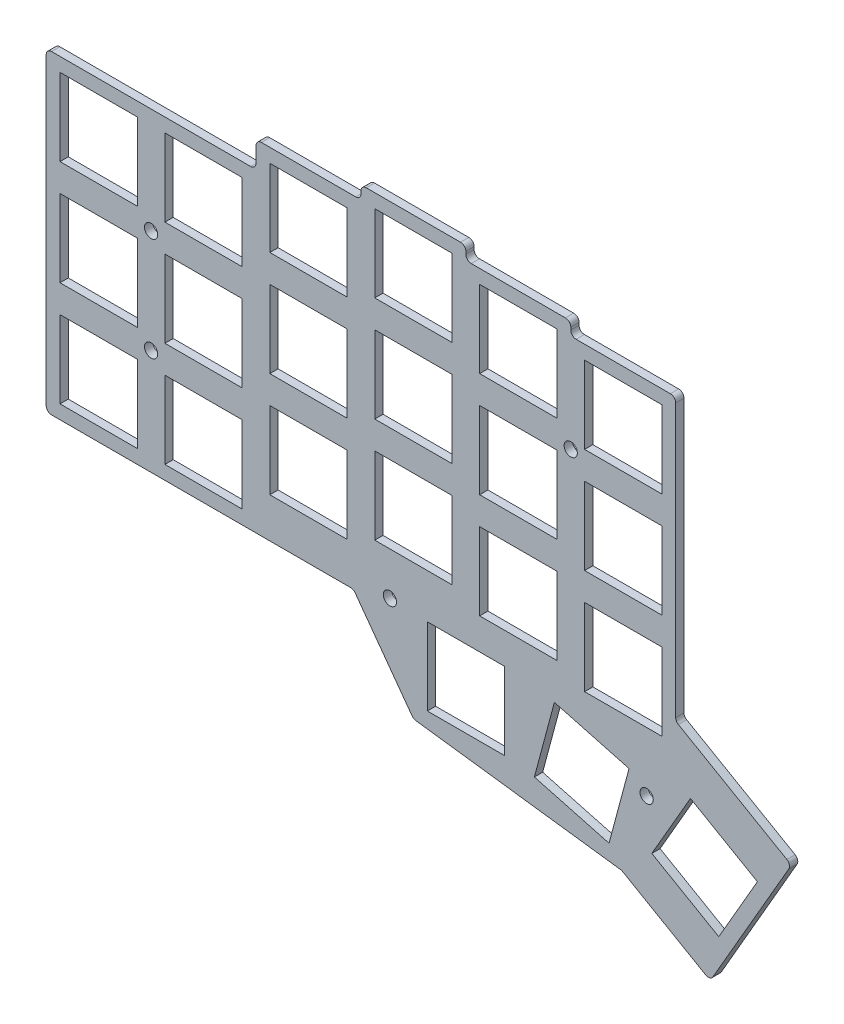
SolidWorks part; units mm, degrees
ref_plane "Front Plane" through (0, 0, 0) normal (0, 0, 1) x (1, 0, 0)
ref_plane "Top Plane" through (0, 0, 0) normal (0, 1, 0) x (1, 0, 0)
ref_plane "Right Plane" through (0, 0, 0) normal (1, 0, 0) x (0, 0, -1)
sketch "Model" plane through (0, 0, 0) normal (0, 0, 1) x (1, 0, 0)
  line L0 (-21.8431, 7.4481) -> (-8.6148, 30.3792)
  line L1 (-38.0636, 15.3297) -> (-23.771, 7.0696)
  line L2 (-75.3888, 20.2293) -> (-38.7189, 15.4592)
  line L3 (-86.2854, 34.8343) -> (-75.7419, 20.3766)
  line L4 (-29.1405, 92.9799) -> (-29.1405, 91.7303)
  line L5 (-8.8891, 91.2299) -> (-28.6402, 91.2299)
  line L6 (-8.3888, 90.7295) -> (-8.3888, 31.2555)
  line L7 (-86.6385, 34.9791) -> (-141.6396, 34.9791)
  line L8 (-142.1399, 90.7295) -> (-142.1399, 35.4795)
  line L9 (-104.6394, 91.2299) -> (-141.6396, 91.2299)
  line L10 (-104.139, 95.4793) -> (-104.139, 91.7303)
  line L11 (-85.6402, 95.9797) -> (-103.6387, 95.9797)
  line L12 (-85.1399, 97.7297) -> (-85.1399, 96.4801)
  line L13 (-67.6393, 98.2301) -> (-84.6395, 98.2301)
  line L14 (-67.1389, 96.4801) -> (-67.1389, 97.7297)
  line L15 (-48.6401, 95.9797) -> (-66.6385, 95.9797)
  line L16 (-48.1397, 93.9807) -> (-48.1397, 95.4793)
  line L17 (-29.6384, 93.4803) -> (-47.6393, 93.4803)
  line L18 (135.1563, 30.6526) -> (116.2359, 41.5721)
  line L19 (123.1828, 7.2669) -> (135.5373, 28.7222)
  line L20 (106.9623, 15.1485) -> (121.2549, 6.8884)
  line L21 (69.6371, 20.0481) -> (106.307, 15.278)
  line L22 (58.7405, 34.6531) -> (69.284, 20.1955)
  line L23 (115.8854, 92.7987) -> (115.8828, 42.2376)
  line L24 (58.3874, 34.7979) -> (3.3863, 34.7979)
  line L25 (2.886, 90.5483) -> (2.886, 35.2983)
  line L26 (40.3865, 91.0487) -> (3.3863, 91.0487)
  line L27 (40.8869, 95.2981) -> (40.8869, 91.5491)
  line L28 (59.3857, 95.7985) -> (41.3872, 95.7985)
  line L29 (59.886, 97.5485) -> (59.886, 96.2989)
  line L30 (77.3866, 98.0489) -> (60.3864, 98.0489)
  line L31 (77.887, 96.2989) -> (77.887, 97.5485)
  line L32 (96.3858, 95.7985) -> (78.3874, 95.7985)
  line L33 (96.8862, 93.7995) -> (96.8862, 95.2981)
  line L34 (115.3875, 93.2991) -> (97.3866, 93.2991)
  line L35 (20.1915, -96.2476) -> (6.9631, -73.3165)
  line L36 (36.4119, -88.366) -> (22.1193, -96.6261)
  line L37 (73.7371, -83.4663) -> (37.0672, -88.2365)
  line L38 (84.6337, -68.8614) -> (74.0902, -83.319)
  line L39 (27.4889, -10.7157) -> (27.4889, -11.9654)
  line L40 (7.2375, -12.4658) -> (26.9885, -12.4658)
  line L41 (6.7371, -12.9662) -> (6.7371, -72.4402)
  line L42 (84.9868, -68.7166) -> (139.9879, -68.7166)
  line L43 (140.4883, -12.9662) -> (140.4883, -68.2162)
  line L44 (102.9878, -12.4658) -> (139.9879, -12.4658)
  line L45 (102.4874, -8.2164) -> (102.4874, -11.9654)
  line L46 (83.9886, -7.716) -> (101.987, -7.716)
  line L47 (83.4882, -5.9659) -> (83.4882, -7.2156)
  line L48 (65.9876, -5.4656) -> (82.9878, -5.4656)
  line L49 (65.4872, -7.2156) -> (65.4872, -5.9659)
  line L50 (46.9884, -7.716) -> (64.9869, -7.716)
  line L51 (46.488, -9.715) -> (46.488, -8.2164)
  line L52 (27.9867, -10.2154) -> (45.9877, -10.2154)
  line L53 (-136.808, -73.043) -> (-117.8876, -62.1236)
  line L54 (-124.8344, -96.4288) -> (-137.189, -74.9734)
  line L55 (-108.614, -88.5472) -> (-122.9066, -96.8073)
  line L56 (-71.2888, -83.6475) -> (-107.9587, -88.4176)
  line L57 (-60.3922, -69.0425) -> (-70.9357, -83.5002)
  line L58 (-117.537, -10.8969) -> (-117.5345, -61.4581)
  line L59 (-60.0391, -68.8978) -> (-5.038, -68.8978)
  line L60 (-4.5376, -13.1474) -> (-4.5376, -68.3974)
  line L61 (-42.0381, -12.647) -> (-5.038, -12.647)
  line L62 (-42.5385, -8.3976) -> (-42.5385, -12.1466)
  line L63 (-61.0373, -7.8972) -> (-43.0389, -7.8972)
  line L64 (-61.5377, -6.1471) -> (-61.5377, -7.3968)
  line L65 (-79.0383, -5.6467) -> (-62.0381, -5.6467)
  line L66 (-79.5387, -7.3968) -> (-79.5387, -6.1471)
  line L67 (-98.0375, -7.8972) -> (-80.039, -7.8972)
  line L68 (-98.5378, -9.8962) -> (-98.5378, -8.3976)
  line L69 (-117.0392, -10.3965) -> (-99.0382, -10.3965)
  line L70 (138.9148, 92.1117) -> (138.9148, 33.3582)
  line L71 (138.1649, 32.9251) -> (119.446, 43.7282)
  line L72 (119.196, 44.1613) -> (119.196, 92.1092)
  line L73 (119.6959, 92.6092) -> (138.4148, 92.6117)
  line L74 (-140.5665, -11.584) -> (-140.5665, -70.3375)
  line L75 (-139.8166, -70.7706) -> (-121.0977, -59.9674)
  line L76 (-120.8476, -59.5344) -> (-120.8476, -11.5865)
  line L77 (-121.3476, -11.0865) -> (-140.0664, -11.084)
  line L78 (18.8966, 74.9256) -> (4.8966, 74.9256)
  line L79 (4.8966, 74.9256) -> (4.8966, 88.9256)
  line L80 (4.8966, 88.9256) -> (18.8966, 88.9256)
  line L81 (18.8966, 88.9256) -> (18.8966, 74.9256)
  line L82 (18.8966, 55.9256) -> (4.8966, 55.9256)
  line L83 (4.8966, 55.9256) -> (4.8966, 69.9256)
  line L84 (4.8966, 69.9256) -> (18.8966, 69.9256)
  line L85 (18.8966, 69.9256) -> (18.8966, 55.9256)
  line L86 (18.8966, 36.9256) -> (4.8966, 36.9256)
  line L87 (4.8966, 36.9256) -> (4.8966, 50.9256)
  line L88 (4.8966, 50.9256) -> (18.8966, 50.9256)
  line L89 (18.8966, 50.9256) -> (18.8966, 36.9256)
  line L90 (37.8948, 74.9262) -> (23.8948, 74.9262)
  line L91 (23.8948, 74.9262) -> (23.8948, 88.9262)
  line L92 (23.8948, 88.9262) -> (37.8948, 88.9262)
  line L93 (37.8948, 88.9262) -> (37.8948, 74.9262)
  line L94 (37.8948, 55.9262) -> (23.8948, 55.9262)
  line L95 (23.8948, 55.9262) -> (23.8948, 69.9262)
  line L96 (23.8948, 69.9262) -> (37.8948, 69.9262)
  line L97 (37.8948, 69.9262) -> (37.8948, 55.9262)
  line L98 (37.8948, 36.9262) -> (23.8948, 36.9262)
  line L99 (23.8948, 36.9262) -> (23.8948, 50.9262)
  line L100 (23.8948, 50.9262) -> (37.8948, 50.9262)
  line L101 (37.8948, 50.9262) -> (37.8948, 36.9262)
  line L102 (56.895, 79.671) -> (42.895, 79.671)
  line L103 (42.895, 79.671) -> (42.895, 93.671)
  line L104 (42.895, 93.671) -> (56.895, 93.671)
  line L105 (56.895, 93.671) -> (56.895, 79.671)
  line L106 (56.895, 60.6711) -> (42.895, 60.6711)
  line L107 (42.895, 60.6711) -> (42.895, 74.6711)
  line L108 (42.895, 74.6711) -> (56.895, 74.6711)
  line L109 (56.895, 74.6711) -> (56.895, 60.6711)
  line L110 (56.895, 41.6711) -> (42.895, 41.6711)
  line L111 (42.895, 41.6711) -> (42.895, 55.6711)
  line L112 (42.895, 55.6711) -> (56.895, 55.6711)
  line L113 (56.895, 55.6711) -> (56.895, 41.6711)
  line L114 (75.897, 82.0499) -> (61.897, 82.0499)
  line L115 (61.897, 82.0499) -> (61.897, 96.0499)
  line L116 (61.897, 96.0499) -> (75.897, 96.0499)
  line L117 (75.897, 96.0499) -> (75.897, 82.0499)
  line L118 (75.897, 63.0499) -> (61.897, 63.0499)
  line L119 (61.897, 63.0499) -> (61.897, 77.0499)
  line L120 (61.897, 77.0499) -> (75.897, 77.0499)
  line L121 (75.897, 77.0499) -> (75.897, 63.0499)
  line L122 (75.897, 44.0499) -> (61.897, 44.0499)
  line L123 (61.897, 44.0499) -> (61.897, 58.0499)
  line L124 (61.897, 58.0499) -> (75.897, 58.0499)
  line L125 (75.897, 58.0499) -> (75.897, 44.0499)
  line L126 (94.8982, 79.6753) -> (80.8982, 79.6753)
  line L127 (80.8982, 79.6753) -> (80.8982, 93.6753)
  line L128 (80.8982, 93.6753) -> (94.8982, 93.6753)
  line L129 (94.8982, 93.6753) -> (94.8982, 79.6753)
  line L130 (94.8982, 60.6753) -> (80.8982, 60.6753)
  line L131 (80.8982, 60.6753) -> (80.8982, 74.6753)
  line L132 (80.8982, 74.6753) -> (94.8982, 74.6753)
  line L133 (94.8982, 74.6753) -> (94.8982, 60.6753)
  line L134 (94.8982, 41.6753) -> (80.8982, 41.6753)
  line L135 (80.8982, 41.6753) -> (80.8982, 55.6753)
  line L136 (80.8982, 55.6753) -> (94.8982, 55.6753)
  line L137 (94.8982, 55.6753) -> (94.8982, 41.6753)
  line L138 (113.9, 77.2905) -> (99.9, 77.2905)
  line L139 (99.9, 77.2905) -> (99.9, 91.2905)
  line L140 (99.9, 91.2905) -> (113.9, 91.2905)
  line L141 (113.9, 91.2905) -> (113.9, 77.2905)
  line L142 (113.9, 58.2905) -> (99.9, 58.2905)
  line L143 (99.9, 58.2905) -> (99.9, 72.2905)
  line L144 (99.9, 72.2905) -> (113.9, 72.2905)
  line L145 (113.9, 72.2905) -> (113.9, 58.2905)
  line L146 (113.9, 39.2905) -> (99.9, 39.2905)
  line L147 (99.9, 39.2905) -> (99.9, 53.2905)
  line L148 (99.9, 53.2905) -> (113.9, 53.2905)
  line L149 (113.9, 53.2905) -> (113.9, 39.2905)
  line L150 (85.4166, 22.0174) -> (71.4166, 22.0174)
  line L151 (71.4166, 22.0174) -> (71.4166, 36.0174)
  line L152 (71.4166, 36.0174) -> (85.4166, 36.0174)
  line L153 (85.4166, 36.0174) -> (85.4166, 22.0174)
  line L154 (104.3289, 17.734) -> (90.806, 21.3575)
  line L155 (90.806, 21.3575) -> (94.4294, 34.8805)
  line L156 (94.4294, 34.8805) -> (107.9524, 31.257)
  line L157 (107.9524, 31.257) -> (104.3289, 17.734)
  line L158 (124.1994, 13.0049) -> (112.075, 20.0049)
  line L159 (112.075, 20.0049) -> (119.075, 32.1293)
  line L160 (119.075, 32.1293) -> (131.1994, 25.1293)
  line L161 (131.1994, 25.1293) -> (124.1994, 13.0049)
  line L162 (-20.5483, -28.7701) -> (-6.5483, -28.7701)
  line L163 (-6.5483, -28.7701) -> (-6.5483, -14.7701)
  line L164 (-6.5483, -14.7701) -> (-20.5483, -14.7701)
  line L165 (-20.5483, -14.7701) -> (-20.5483, -28.7701)
  line L166 (-20.5483, -47.7701) -> (-6.5483, -47.7701)
  line L167 (-6.5483, -47.7701) -> (-6.5483, -33.7701)
  line L168 (-6.5483, -33.7701) -> (-20.5483, -33.7701)
  line L169 (-20.5483, -33.7701) -> (-20.5483, -47.7701)
  line L170 (-20.5483, -66.7701) -> (-6.5483, -66.7701)
  line L171 (-6.5483, -66.7701) -> (-6.5483, -52.7701)
  line L172 (-6.5483, -52.7701) -> (-20.5483, -52.7701)
  line L173 (-20.5483, -52.7701) -> (-20.5483, -66.7701)
  line L174 (-39.5464, -28.7694) -> (-25.5464, -28.7694)
  line L175 (-25.5464, -28.7694) -> (-25.5464, -14.7694)
  line L176 (-25.5464, -14.7694) -> (-39.5464, -14.7694)
  line L177 (-39.5464, -14.7694) -> (-39.5464, -28.7694)
  line L178 (-39.5464, -47.7694) -> (-25.5464, -47.7694)
  line L179 (-25.5464, -47.7694) -> (-25.5464, -33.7694)
  line L180 (-25.5464, -33.7694) -> (-39.5464, -33.7694)
  line L181 (-39.5464, -33.7694) -> (-39.5464, -47.7694)
  line L182 (-39.5464, -66.7694) -> (-25.5464, -66.7694)
  line L183 (-25.5464, -66.7694) -> (-25.5464, -52.7694)
  line L184 (-25.5464, -52.7694) -> (-39.5464, -52.7694)
  line L185 (-39.5464, -52.7694) -> (-39.5464, -66.7694)
  line L186 (-58.5467, -24.0246) -> (-44.5467, -24.0246)
  line L187 (-44.5467, -24.0246) -> (-44.5467, -10.0246)
  line L188 (-44.5467, -10.0246) -> (-58.5467, -10.0246)
  line L189 (-58.5467, -10.0246) -> (-58.5467, -24.0246)
  line L190 (-58.5467, -43.0246) -> (-44.5467, -43.0246)
  line L191 (-44.5467, -43.0246) -> (-44.5467, -29.0246)
  line L192 (-44.5467, -29.0246) -> (-58.5467, -29.0246)
  line L193 (-58.5467, -29.0246) -> (-58.5467, -43.0246)
  line L194 (-58.5467, -62.0246) -> (-44.5467, -62.0246)
  line L195 (-44.5467, -62.0246) -> (-44.5467, -48.0246)
  line L196 (-44.5467, -48.0246) -> (-58.5467, -48.0246)
  line L197 (-58.5467, -48.0246) -> (-58.5467, -62.0246)
  line L198 (-77.5486, -21.6458) -> (-63.5486, -21.6458)
  line L199 (-63.5486, -21.6458) -> (-63.5486, -7.6458)
  line L200 (-63.5486, -7.6458) -> (-77.5486, -7.6458)
  line L201 (-77.5486, -7.6458) -> (-77.5486, -21.6458)
  line L202 (-77.5486, -40.6458) -> (-63.5486, -40.6458)
  line L203 (-63.5486, -40.6458) -> (-63.5486, -26.6458)
  line L204 (-63.5486, -26.6458) -> (-77.5486, -26.6458)
  line L205 (-77.5486, -26.6458) -> (-77.5486, -40.6458)
  line L206 (-77.5486, -59.6458) -> (-63.5486, -59.6458)
  line L207 (-63.5486, -59.6458) -> (-63.5486, -45.6458)
  line L208 (-63.5486, -45.6458) -> (-77.5486, -45.6458)
  line L209 (-77.5486, -45.6458) -> (-77.5486, -59.6458)
  line L210 (-96.5499, -24.0204) -> (-82.5499, -24.0204)
  line L211 (-82.5499, -24.0204) -> (-82.5499, -10.0204)
  line L212 (-82.5499, -10.0204) -> (-96.5499, -10.0204)
  line L213 (-96.5499, -10.0204) -> (-96.5499, -24.0204)
  line L214 (-96.5499, -43.0203) -> (-82.5499, -43.0203)
  line L215 (-82.5499, -43.0203) -> (-82.5499, -29.0203)
  line L216 (-82.5499, -29.0203) -> (-96.5499, -29.0203)
  line L217 (-96.5499, -29.0203) -> (-96.5499, -43.0203)
  line L218 (-96.5499, -62.0203) -> (-82.5499, -62.0203)
  line L219 (-82.5499, -62.0203) -> (-82.5499, -48.0203)
  line L220 (-82.5499, -48.0203) -> (-96.5499, -48.0203)
  line L221 (-96.5499, -48.0203) -> (-96.5499, -62.0203)
  line L222 (-115.5516, -26.4052) -> (-101.5516, -26.4052)
  line L223 (-101.5516, -26.4052) -> (-101.5516, -12.4052)
  line L224 (-101.5516, -12.4052) -> (-115.5516, -12.4052)
  line L225 (-115.5516, -12.4052) -> (-115.5516, -26.4052)
  line L226 (-115.5516, -45.4052) -> (-101.5516, -45.4052)
  line L227 (-101.5516, -45.4052) -> (-101.5516, -31.4052)
  line L228 (-101.5516, -31.4052) -> (-115.5516, -31.4052)
  line L229 (-115.5516, -31.4052) -> (-115.5516, -45.4052)
  line L230 (-115.5516, -64.4052) -> (-101.5516, -64.4052)
  line L231 (-101.5516, -64.4052) -> (-101.5516, -50.4052)
  line L232 (-101.5516, -50.4052) -> (-115.5516, -50.4052)
  line L233 (-115.5516, -50.4052) -> (-115.5516, -64.4052)
  line L234 (-87.0683, -81.6783) -> (-73.0683, -81.6783)
  line L235 (-73.0683, -81.6783) -> (-73.0683, -67.6783)
  line L236 (-73.0683, -67.6783) -> (-87.0683, -67.6783)
  line L237 (-87.0683, -67.6783) -> (-87.0683, -81.6783)
  line L238 (-105.9806, -85.9616) -> (-92.4576, -82.3382)
  line L239 (-92.4576, -82.3382) -> (-96.0811, -68.8152)
  line L240 (-96.0811, -68.8152) -> (-109.6041, -72.4387)
  line L241 (-109.6041, -72.4387) -> (-105.9806, -85.9616)
  line L242 (-125.851, -90.6908) -> (-113.7267, -83.6908)
  line L243 (-113.7267, -83.6908) -> (-120.7267, -71.5664)
  line L244 (-120.7267, -71.5664) -> (-132.851, -78.5664)
  line L245 (-132.851, -78.5664) -> (-125.851, -90.6908)
  spline S0 degree 3 poles (-8.6153, 30.3807) (-8.4626, 30.6458) (-8.3842, 30.9472) (-8.3882, 31.2532) knots 0 0 0 0 1 1 1 1
  spline S1 degree 3 poles (-21.8439, 7.4422) (-21.8429, 7.4437) (-21.8419, 7.4453) (-21.8408, 7.4468) knots 1 1 1 1 2 2 2 2
  spline S2 degree 3 poles (-23.769, 7.0673) (-23.1339, 6.6392) (-22.272, 6.8071) (-21.8439, 7.4422) knots 0 0 0 0 1 1 1 1
  spline S3 degree 3 poles (-38.063, 15.3284) (-38.2765, 15.3928) (-38.4957, 15.4362) (-38.7176, 15.4579) knots 0 0 0 0 1 1 1 1
  spline S4 degree 3 poles (-75.7416, 20.3746) (-75.6478, 20.2809) (-75.5206, 20.2283) (-75.3881, 20.2283) knots 0 0 0 0 1 1 1 1
  spline S5 degree 3 poles (-29.1383, 92.9782) (-29.1382, 93.2543) (-29.362, 93.4782) (-29.6381, 93.4783) knots 0 0 0 0 1 1 1 1
  spline S6 degree 3 poles (-29.1383, 91.7282) (-29.1383, 91.4521) (-28.9145, 91.2282) (-28.6384, 91.2281) (-28.6383, 91.2281) (-28.6382, 91.2281) (-28.6381, 91.2281) knots 0 0 0 0 1 1 1 2 2 2 2
  spline S7 degree 3 poles (-86.2846, 34.8318) (-86.3784, 34.9256) (-86.5056, 34.9783) (-86.6385, 34.9791) knots 0 0 0 0 1 1 1 1
  spline S8 degree 3 poles (-142.1382, 35.4782) (-142.1381, 35.2021) (-141.9142, 34.9783) (-141.6381, 34.9783) knots 0 0 0 0 1 1 1 1
  spline S9 degree 3 poles (-141.638, 91.2281) (-141.9142, 91.2282) (-142.1381, 91.0044) (-142.1382, 90.7282) knots 0 0 0 0 1 1 1 1
  spline S10 degree 3 poles (-104.6382, 91.2281) (-104.362, 91.228) (-104.1381, 91.4518) (-104.138, 91.728) (-104.138, 91.7281) (-104.138, 91.7281) (-104.138, 91.7282) knots 0 0 0 0 1 1 1 2 2 2 2
  spline S11 degree 3 poles (-103.6382, 95.9781) (-103.9142, 95.9781) (-104.138, 95.7543) (-104.138, 95.4783) knots 0 0 0 0 1 1 1 1
  spline S12 degree 3 poles (-85.6382, 95.9781) (-85.3621, 95.9781) (-85.1382, 96.2019) (-85.1381, 96.478) (-85.1381, 96.4781) (-85.1381, 96.4782) (-85.1381, 96.4783) knots 0 0 0 0 1 1 1 2 2 2 2
  spline S13 degree 3 poles (-84.6382, 98.2283) (-84.9144, 98.2283) (-85.1382, 98.0044) (-85.1381, 97.7282) knots 0 0 0 0 1 1 1 1
  spline S14 degree 3 poles (-67.1381, 97.7282) (-67.1381, 98.0043) (-67.3619, 98.2283) (-67.638, 98.2283) knots 0 0 0 0 2 2 2 2
  spline S15 degree 3 poles (-67.1381, 96.4783) (-67.1382, 96.2021) (-66.9144, 95.9782) (-66.6383, 95.9781) (-66.6382, 95.9781) (-66.6381, 95.9781) (-66.638, 95.9781) knots 0 0 0 0 1 1 1 2 2 2 2
  spline S16 degree 3 poles (-48.1382, 95.4783) (-48.1383, 95.7543) (-48.362, 95.9781) (-48.6381, 95.9781) knots 0 0 0 0 1 1 1 1
  spline S17 degree 3 poles (-48.1382, 93.9782) (-48.1381, 93.702) (-47.9142, 93.4782) (-47.6381, 93.4783) knots 0 0 0 0 1 1 1 1
  spline S18 degree 3 poles (-8.3882, 90.7282) (-8.3883, 91.0043) (-8.6121, 91.228) (-8.8881, 91.2281) knots 0 0 0 0 1 1 1 1
  spline S19 degree 3 poles (115.8851, 42.2368) (115.8929, 41.9725) (116.0232, 41.7268) (116.2377, 41.5721) knots 0 0 0 0 1 1 1 1
  spline S20 degree 3 poles (135.163, 30.647) (135.1614, 30.648) (135.1599, 30.6491) (135.1583, 30.6501) knots 1 1 1 1 2 2 2 2
  spline S21 degree 3 poles (135.5373, 28.7222) (135.9659, 29.3571) (135.7981, 30.2189) (135.163, 30.647) knots 0 0 0 0 1 1 1 1
  spline S22 degree 3 poles (123.182, 7.261) (123.183, 7.2625) (123.184, 7.2641) (123.1851, 7.2656) knots 1 1 1 1 2 2 2 2
  spline S23 degree 3 poles (121.2569, 6.8861) (121.892, 6.4581) (122.7539, 6.6259) (123.182, 7.261) knots 0 0 0 0 1 1 1 1
  spline S24 degree 3 poles (106.9629, 15.1472) (106.7494, 15.2117) (106.5302, 15.255) (106.3083, 15.2768) knots 0 0 0 0 1 1 1 1
  spline S25 degree 3 poles (69.2843, 20.1934) (69.3781, 20.0997) (69.5053, 20.0471) (69.6378, 20.0471) knots 0 0 0 0 1 1 1 1
  spline S26 degree 3 poles (115.8876, 92.797) (115.8877, 93.0731) (115.6639, 93.297) (115.3878, 93.2971) knots 0 0 0 0 1 1 1 1
  spline S27 degree 3 poles (58.7413, 34.6506) (58.6475, 34.7444) (58.5203, 34.7971) (58.3874, 34.7979) knots 0 0 0 0 1 1 1 1
  spline S28 degree 3 poles (2.8877, 35.297) (2.8878, 35.0209) (3.1117, 34.7971) (3.3878, 34.7971) knots 0 0 0 0 1 1 1 1
  spline S29 degree 3 poles (3.3879, 91.0469) (3.1117, 91.047) (2.8878, 90.8232) (2.8877, 90.547) knots 0 0 0 0 1 1 1 1
  spline S30 degree 3 poles (40.3877, 91.0469) (40.6639, 91.0468) (40.8878, 91.2706) (40.8879, 91.5468) (40.8879, 91.5469) (40.8879, 91.5469) (40.8879, 91.547) knots 0 0 0 0 1 1 1 2 2 2 2
  spline S31 degree 3 poles (41.3877, 95.797) (41.1117, 95.7969) (40.8879, 95.5731) (40.8879, 95.2971) knots 0 0 0 0 1 1 1 1
  spline S32 degree 3 poles (59.3877, 95.797) (59.6638, 95.7969) (59.8877, 96.0207) (59.8878, 96.2968) (59.8878, 96.2969) (59.8878, 96.297) (59.8878, 96.2971) knots 0 0 0 0 1 1 1 2 2 2 2
  spline S33 degree 3 poles (60.3877, 98.0471) (60.1115, 98.0471) (59.8877, 97.8232) (59.8878, 97.547) knots 0 0 0 0 1 1 1 1
  spline S34 degree 3 poles (77.8878, 97.547) (77.8878, 97.8232) (77.664, 98.0471) (77.3879, 98.0471) knots 0 0 0 0 2 2 2 2
  spline S35 degree 3 poles (77.8878, 96.2971) (77.8877, 96.0209) (78.1115, 95.797) (78.3876, 95.797) (78.3877, 95.797) (78.3878, 95.797) (78.3879, 95.797) knots 0 0 0 0 1 1 1 2 2 2 2
  spline S36 degree 3 poles (96.8877, 95.2971) (96.8876, 95.5731) (96.6639, 95.7969) (96.3878, 95.797) knots 0 0 0 0 1 1 1 1
  spline S37 degree 3 poles (96.8877, 93.797) (96.8878, 93.5208) (97.1117, 93.297) (97.3878, 93.2971) knots 0 0 0 0 1 1 1 1
  spline S38 degree 3 poles (6.9637, -73.315) (6.8109, -73.0499) (6.7325, -72.7484) (6.7366, -72.4425) knots 0 0 0 0 1 1 1 1
  spline S39 degree 3 poles (20.1923, -96.2535) (20.1912, -96.252) (20.1902, -96.2504) (20.1892, -96.2489) knots 1 1 1 1 2 2 2 2
  spline S40 degree 3 poles (22.1173, -96.6284) (21.4822, -97.0564) (20.6203, -96.8886) (20.1923, -96.2535) knots 0 0 0 0 1 1 1 1
  spline S41 degree 3 poles (36.4114, -88.3673) (36.6248, -88.3028) (36.844, -88.2594) (37.0659, -88.2377) knots 0 0 0 0 1 1 1 1
  spline S42 degree 3 poles (74.0899, -83.3211) (73.9962, -83.4148) (73.869, -83.4674) (73.7364, -83.4674) knots 0 0 0 0 1 1 1 1
  spline S43 degree 3 poles (27.4866, -10.7175) (27.4865, -10.4414) (27.7103, -10.2175) (27.9865, -10.2174) knots 0 0 0 0 1 1 1 1
  spline S44 degree 3 poles (27.4866, -11.9674) (27.4866, -12.2436) (27.2628, -12.4675) (26.9867, -12.4676) (26.9866, -12.4676) (26.9865, -12.4676) (26.9865, -12.4676) knots 0 0 0 0 1 1 1 2 2 2 2
  spline S45 degree 3 poles (84.633, -68.8639) (84.7267, -68.7701) (84.8539, -68.7174) (84.9868, -68.7166) knots 0 0 0 0 1 1 1 1
  spline S46 degree 3 poles (140.4865, -68.2175) (140.4864, -68.4936) (140.2625, -68.7174) (139.9864, -68.7173) knots 0 0 0 0 1 1 1 1
  spline S47 degree 3 poles (139.9864, -12.4676) (140.2625, -12.4675) (140.4864, -12.6913) (140.4865, -12.9674) knots 0 0 0 0 1 1 1 1
  spline S48 degree 3 poles (102.9865, -12.4676) (102.7103, -12.4676) (102.4864, -12.2438) (102.4864, -11.9677) (102.4864, -11.9676) (102.4864, -11.9675) (102.4864, -11.9674) knots 0 0 0 0 1 1 1 2 2 2 2
  spline S49 degree 3 poles (101.9865, -7.7175) (102.2625, -7.7176) (102.4863, -7.9413) (102.4864, -8.2174) knots 0 0 0 0 1 1 1 1
  spline S50 degree 3 poles (83.9865, -7.7175) (83.7104, -7.7176) (83.4865, -7.4938) (83.4864, -7.2176) (83.4864, -7.2176) (83.4864, -7.2175) (83.4864, -7.2174) knots 0 0 0 0 1 1 1 2 2 2 2
  spline S51 degree 3 poles (82.9865, -5.4673) (83.2627, -5.4674) (83.4865, -5.6913) (83.4864, -5.9675) knots 0 0 0 0 1 1 1 1
  spline S52 degree 3 poles (65.4865, -5.9675) (65.4864, -5.6913) (65.7102, -5.4674) (65.9863, -5.4673) knots 0 0 0 0 2 2 2 2
  spline S53 degree 3 poles (65.4865, -7.2174) (65.4865, -7.4935) (65.2627, -7.7174) (64.9866, -7.7175) (64.9865, -7.7175) (64.9864, -7.7175) (64.9863, -7.7175) knots 0 0 0 0 1 1 1 2 2 2 2
  spline S54 degree 3 poles (46.4865, -8.2174) (46.4866, -7.9413) (46.7103, -7.7176) (46.9864, -7.7175) knots 0 0 0 0 1 1 1 1
  spline S55 degree 3 poles (46.4865, -9.7175) (46.4865, -9.9937) (46.2625, -10.2175) (45.9864, -10.2174) knots 0 0 0 0 1 1 1 1
  spline S56 degree 3 poles (6.7366, -12.9674) (6.7366, -12.6914) (6.9604, -12.4676) (7.2365, -12.4676) knots 0 0 0 0 1 1 1 1
  spline S57 degree 3 poles (-117.5368, -61.4589) (-117.5446, -61.7232) (-117.6748, -61.9689) (-117.8893, -62.1236) knots 0 0 0 0 1 1 1 1
  spline S58 degree 3 poles (-136.8146, -73.0487) (-136.8131, -73.0476) (-136.8116, -73.0466) (-136.81, -73.0456) knots 1 1 1 1 2 2 2 2
  spline S59 degree 3 poles (-137.189, -74.9734) (-137.6176, -74.3386) (-137.4497, -73.4767) (-136.8146, -73.0487) knots 0 0 0 0 1 1 1 1
  spline S60 degree 3 poles (-124.8336, -96.4347) (-124.8347, -96.4331) (-124.8357, -96.4316) (-124.8367, -96.4301) knots 1 1 1 1 2 2 2 2
  spline S61 degree 3 poles (-122.9086, -96.8095) (-123.5437, -97.2376) (-124.4056, -97.0698) (-124.8336, -96.4347) knots 0 0 0 0 1 1 1 1
  spline S62 degree 3 poles (-108.6145, -88.5485) (-108.4011, -88.484) (-108.1819, -88.4406) (-107.96, -88.4189) knots 0 0 0 0 1 1 1 1
  spline S63 degree 3 poles (-70.936, -83.5022) (-71.0297, -83.596) (-71.1569, -83.6486) (-71.2895, -83.6485) knots 0 0 0 0 1 1 1 1
  spline S64 degree 3 poles (-117.5393, -10.8987) (-117.5394, -10.6226) (-117.3156, -10.3987) (-117.0394, -10.3986) knots 0 0 0 0 1 1 1 1
  spline S65 degree 3 poles (-60.3929, -69.0451) (-60.2992, -68.9513) (-60.172, -68.8986) (-60.0391, -68.8978) knots 0 0 0 0 1 1 1 1
  spline S66 degree 3 poles (-4.5394, -68.3987) (-4.5395, -68.6748) (-4.7634, -68.8986) (-5.0395, -68.8985) knots 0 0 0 0 1 1 1 1
  spline S67 degree 3 poles (-5.0395, -12.6488) (-4.7634, -12.6487) (-4.5395, -12.8725) (-4.5394, -13.1486) knots 0 0 0 0 1 1 1 1
  spline S68 degree 3 poles (-42.0394, -12.6488) (-42.3156, -12.6488) (-42.5395, -12.425) (-42.5395, -12.1489) (-42.5395, -12.1488) (-42.5395, -12.1487) (-42.5395, -12.1486) knots 0 0 0 0 1 1 1 2 2 2 2
  spline S69 degree 3 poles (-43.0394, -7.8987) (-42.7634, -7.8988) (-42.5396, -8.1225) (-42.5395, -8.3986) knots 0 0 0 0 1 1 1 1
  spline S70 degree 3 poles (-61.0394, -7.8987) (-61.3155, -7.8988) (-61.5394, -7.675) (-61.5395, -7.3988) (-61.5395, -7.3988) (-61.5395, -7.3987) (-61.5395, -7.3986) knots 0 0 0 0 1 1 1 2 2 2 2
  spline S71 degree 3 poles (-62.0394, -5.6485) (-61.7632, -5.6486) (-61.5394, -5.8725) (-61.5395, -6.1486) knots 0 0 0 0 1 1 1 1
  spline S72 degree 3 poles (-79.5394, -6.1486) (-79.5395, -5.8725) (-79.3157, -5.6486) (-79.0396, -5.6485) knots 0 0 0 0 2 2 2 2
  spline S73 degree 3 poles (-79.5394, -7.3986) (-79.5394, -7.6747) (-79.7632, -7.8986) (-80.0393, -7.8987) (-80.0394, -7.8987) (-80.0395, -7.8987) (-80.0396, -7.8987) knots 0 0 0 0 1 1 1 2 2 2 2
  spline S74 degree 3 poles (-98.5394, -8.3986) (-98.5393, -8.1225) (-98.3156, -7.8988) (-98.0395, -7.8987) knots 0 0 0 0 1 1 1 1
  spline S75 degree 3 poles (-98.5394, -9.8987) (-98.5394, -10.1748) (-98.7634, -10.3986) (-99.0395, -10.3986) knots 0 0 0 0 1 1 1 1
  spline S76 degree 3 poles (-123.6381, 52.6314) (-124.2456, 52.6314) (-124.7381, 53.1239) (-124.7381, 53.7314) (-124.7381, 54.3389) (-124.2456, 54.8314) (-123.6381, 54.8314) knots 2 2 2 2 3 3 3 4 4 4 4
  spline S77 degree 3 poles (-123.6381, 54.8314) (-123.0306, 54.8314) (-122.5381, 54.3389) (-122.5381, 53.7314) (-122.5381, 53.1239) (-123.0306, 52.6314) (-123.6381, 52.6314) knots 0 0 0 0 1 1 1 2 2 2 2
  spline S78 degree 3 poles (-123.6381, 71.3814) (-124.2456, 71.3814) (-124.7381, 71.8739) (-124.7381, 72.4814) (-124.7381, 73.0889) (-124.2456, 73.5814) (-123.6381, 73.5814) knots 2 2 2 2 3 3 3 4 4 4 4
  spline S79 degree 3 poles (-123.6381, 73.5814) (-123.0306, 73.5814) (-122.5381, 73.0889) (-122.5381, 72.4814) (-122.5381, 71.8739) (-123.0306, 71.3814) (-123.6381, 71.3814) knots 0 0 0 0 1 1 1 2 2 2 2
  spline S80 degree 3 poles (-47.6381, 75.1312) (-48.2456, 75.1312) (-48.7381, 75.6237) (-48.7381, 76.2312) (-48.7381, 76.8387) (-48.2456, 77.3312) (-47.6381, 77.3312) knots 2 2 2 2 3 3 3 4 4 4 4
  spline S81 degree 3 poles (-47.6381, 77.3312) (-47.0306, 77.3312) (-46.5381, 76.8387) (-46.5381, 76.2312) (-46.5381, 75.6237) (-47.0306, 75.1312) (-47.6381, 75.1312) knots 0 0 0 0 1 1 1 2 2 2 2
  spline S82 degree 3 poles (-80.388, 35.3813) (-80.9956, 35.3813) (-81.488, 35.8738) (-81.488, 36.4813) (-81.488, 37.0888) (-80.9956, 37.5813) (-80.388, 37.5813) knots 2 2 2 2 3 3 3 4 4 4 4
  spline S83 degree 3 poles (-80.388, 37.5813) (-79.7805, 37.5813) (-79.288, 37.0888) (-79.288, 36.4813) (-79.288, 35.8738) (-79.7805, 35.3813) (-80.388, 35.3813) knots 0 0 0 0 1 1 1 2 2 2 2
  spline S84 degree 3 poles (-33.8881, 27.6312) (-34.4956, 27.6312) (-34.9881, 28.1237) (-34.9881, 28.7312) (-34.9881, 29.3388) (-34.4956, 29.8312) (-33.8881, 29.8312) knots 2 2 2 2 3 3 3 4 4 4 4
  spline S85 degree 3 poles (-33.8881, 29.8312) (-33.2805, 29.8312) (-32.7881, 29.3388) (-32.7881, 28.7312) (-32.7881, 28.1237) (-33.2805, 27.6312) (-33.8881, 27.6312) knots 0 0 0 0 1 1 1 2 2 2 2
  spline S86 degree 3 poles (21.3878, 52.4502) (20.7803, 52.4502) (20.2878, 52.9427) (20.2878, 53.5502) (20.2878, 54.1578) (20.7803, 54.6502) (21.3878, 54.6502) knots 2 2 2 2 3 3 3 4 4 4 4
  spline S87 degree 3 poles (21.3878, 54.6502) (21.9953, 54.6502) (22.4878, 54.1578) (22.4878, 53.5502) (22.4878, 52.9427) (21.9953, 52.4502) (21.3878, 52.4502) knots 0 0 0 0 1 1 1 2 2 2 2
  spline S88 degree 3 poles (97.3878, 74.95) (96.7803, 74.95) (96.2878, 75.4425) (96.2878, 76.05) (96.2878, 76.6575) (96.7803, 77.15) (97.3878, 77.15) knots 2 2 2 2 3 3 3 4 4 4 4
  spline S89 degree 3 poles (97.3878, 77.15) (97.9953, 77.15) (98.4878, 76.6575) (98.4878, 76.05) (98.4878, 75.4425) (97.9953, 74.95) (97.3878, 74.95) knots 0 0 0 0 1 1 1 2 2 2 2
  spline S90 degree 3 poles (64.6379, 35.2001) (64.0303, 35.2001) (63.5379, 35.6926) (63.5379, 36.3001) (63.5379, 36.9076) (64.0303, 37.4001) (64.6379, 37.4001) knots 2 2 2 2 3 3 3 4 4 4 4
  spline S91 degree 3 poles (64.6379, 37.4001) (65.2454, 37.4001) (65.7379, 36.9076) (65.7379, 36.3001) (65.7379, 35.6926) (65.2454, 35.2001) (64.6379, 35.2001) knots 0 0 0 0 1 1 1 2 2 2 2
  spline S92 degree 3 poles (111.1378, 27.4501) (110.5303, 27.4501) (110.0378, 27.9425) (110.0378, 28.5501) (110.0378, 29.1576) (110.5303, 29.65) (111.1378, 29.65) knots 2 2 2 2 3 3 3 4 4 4 4
  spline S93 degree 3 poles (111.1378, 29.65) (111.7454, 29.65) (112.2378, 29.1576) (112.2378, 28.5501) (112.2378, 27.9425) (111.7454, 27.4501) (111.1378, 27.4501) knots 0 0 0 0 1 1 1 2 2 2 2
  spline S94 degree 3 poles (121.9864, -51.0642) (122.5939, -51.0642) (123.0864, -50.5718) (123.0864, -49.9642) (123.0864, -49.3567) (122.5939, -48.8642) (121.9864, -48.8642) knots 2 2 2 2 3 3 3 4 4 4 4
  spline S95 degree 3 poles (121.9864, -48.8642) (121.3789, -48.8642) (120.8864, -49.3567) (120.8864, -49.9642) (120.8864, -50.5718) (121.3789, -51.0642) (121.9864, -51.0642) knots 0 0 0 0 1 1 1 2 2 2 2
  spline S96 degree 3 poles (121.9864, -32.3142) (122.5939, -32.3142) (123.0864, -31.8218) (123.0864, -31.2142) (123.0864, -30.6067) (122.5939, -30.1142) (121.9864, -30.1142) knots 2 2 2 2 3 3 3 4 4 4 4
  spline S97 degree 3 poles (121.9864, -30.1142) (121.3789, -30.1142) (120.8864, -30.6067) (120.8864, -31.2142) (120.8864, -31.8218) (121.3789, -32.3142) (121.9864, -32.3142) knots 0 0 0 0 1 1 1 2 2 2 2
  spline S98 degree 3 poles (45.9864, -28.5644) (46.5939, -28.5644) (47.0864, -28.072) (47.0864, -27.4644) (47.0864, -26.8569) (46.5939, -26.3644) (45.9864, -26.3644) knots 2 2 2 2 3 3 3 4 4 4 4
  spline S99 degree 3 poles (45.9864, -26.3644) (45.3789, -26.3644) (44.8864, -26.8569) (44.8864, -27.4644) (44.8864, -28.072) (45.3789, -28.5644) (45.9864, -28.5644) knots 0 0 0 0 1 1 1 2 2 2 2
  spline S100 degree 3 poles (78.7364, -68.3144) (79.3439, -68.3144) (79.8364, -67.8219) (79.8364, -67.2144) (79.8364, -66.6069) (79.3439, -66.1144) (78.7364, -66.1144) knots 2 2 2 2 3 3 3 4 4 4 4
  spline S101 degree 3 poles (78.7364, -66.1144) (78.1288, -66.1144) (77.6364, -66.6069) (77.6364, -67.2144) (77.6364, -67.8219) (78.1288, -68.3144) (78.7364, -68.3144) knots 0 0 0 0 1 1 1 2 2 2 2
  spline S102 degree 3 poles (32.2364, -76.0644) (32.8439, -76.0644) (33.3364, -75.5719) (33.3364, -74.9644) (33.3364, -74.3569) (32.8439, -73.8644) (32.2364, -73.8644) knots 2 2 2 2 3 3 3 4 4 4 4
  spline S103 degree 3 poles (32.2364, -73.8644) (31.6289, -73.8644) (31.1364, -74.3569) (31.1364, -74.9644) (31.1364, -75.5719) (31.6289, -76.0644) (32.2364, -76.0644) knots 0 0 0 0 1 1 1 2 2 2 2
  spline S104 degree 3 poles (-23.0395, -51.2454) (-22.432, -51.2454) (-21.9395, -50.7529) (-21.9395, -50.1454) (-21.9395, -49.5379) (-22.432, -49.0454) (-23.0395, -49.0454) knots 2 2 2 2 3 3 3 4 4 4 4
  spline S105 degree 3 poles (-23.0395, -49.0454) (-23.647, -49.0454) (-24.1395, -49.5379) (-24.1395, -50.1454) (-24.1395, -50.7529) (-23.647, -51.2454) (-23.0395, -51.2454) knots 0 0 0 0 1 1 1 2 2 2 2
  spline S106 degree 3 poles (-99.0395, -28.7456) (-98.432, -28.7456) (-97.9395, -28.2531) (-97.9395, -27.6456) (-97.9395, -27.0381) (-98.432, -26.5456) (-99.0395, -26.5456) knots 2 2 2 2 3 3 3 4 4 4 4
  spline S107 degree 3 poles (-99.0395, -26.5456) (-99.647, -26.5456) (-100.1395, -27.0381) (-100.1395, -27.6456) (-100.1395, -28.2531) (-99.647, -28.7456) (-99.0395, -28.7456) knots 0 0 0 0 1 1 1 2 2 2 2
  spline S108 degree 3 poles (-66.2895, -68.4956) (-65.682, -68.4956) (-65.1895, -68.0031) (-65.1895, -67.3956) (-65.1895, -66.7881) (-65.682, -66.2956) (-66.2895, -66.2956) knots 2 2 2 2 3 3 3 4 4 4 4
  spline S109 degree 3 poles (-66.2895, -66.2956) (-66.8971, -66.2956) (-67.3895, -66.7881) (-67.3895, -67.3956) (-67.3895, -68.0031) (-66.8971, -68.4956) (-66.2895, -68.4956) knots 0 0 0 0 1 1 1 2 2 2 2
  spline S110 degree 3 poles (-112.7895, -76.2456) (-112.182, -76.2456) (-111.6895, -75.7531) (-111.6895, -75.1456) (-111.6895, -74.5381) (-112.182, -74.0456) (-112.7895, -74.0456) knots 2 2 2 2 3 3 3 4 4 4 4
  spline S111 degree 3 poles (-112.7895, -74.0456) (-113.397, -74.0456) (-113.8895, -74.5381) (-113.8895, -75.1456) (-113.8895, -75.7531) (-113.397, -76.2456) (-112.7895, -76.2456) knots 0 0 0 0 1 1 1 2 2 2 2
  spline S112 degree 3 poles (138.9148, 33.3582) (138.9148, 32.9733) (138.4982, 32.7327) (138.1649, 32.9251) knots 1 1 1 1 2 2 2 2
  spline S113 degree 3 poles (119.446, 43.7282) (119.2913, 43.8175) (119.196, 43.9826) (119.196, 44.1613) knots 3 3 3 3 4 4 4 4
  spline S114 degree 3 poles (119.196, 92.1092) (119.196, 92.3853) (119.4198, 92.6092) (119.6959, 92.6092) knots 5 5 5 5 6 6 6 6
  spline S115 degree 3 poles (138.4148, 92.6117) (138.6909, 92.6117) (138.9148, 92.3879) (138.9148, 92.1117) knots 7 7 7 7 8 8 8 8
  spline S116 degree 3 poles (-140.5665, -70.3375) (-140.5665, -70.7224) (-140.1499, -70.9629) (-139.8166, -70.7706) knots 1 1 1 1 2 2 2 2
  spline S117 degree 3 poles (-121.0977, -59.9674) (-120.943, -59.8781) (-120.8476, -59.7131) (-120.8476, -59.5344) knots 3 3 3 3 4 4 4 4
  spline S118 degree 3 poles (-120.8476, -11.5865) (-120.8476, -11.3103) (-121.0715, -11.0865) (-121.3476, -11.0865) knots 5 5 5 5 6 6 6 6
  spline S119 degree 3 poles (-140.0664, -11.084) (-140.3426, -11.0839) (-140.5665, -11.3078) (-140.5665, -11.584) knots 7 7 7 7 8 8 8 8
  spline S120 degree 3 poles (120.7443, 45.1272) (120.7443, 45.7347) (121.2368, 46.2272) (121.8443, 46.2272) (122.4518, 46.2272) (122.9443, 45.7347) (122.9443, 45.1272) knots 2 2 2 2 3 3 3 4 4 4 4
  spline S121 degree 3 poles (122.9443, 45.1272) (122.9443, 44.5197) (122.4518, 44.0272) (121.8443, 44.0272) (121.2368, 44.0272) (120.7443, 44.5197) (120.7443, 45.1272) knots 0 0 0 0 1 1 1 2 2 2 2
  spline S122 degree 3 poles (135.1763, 36.6063) (135.1763, 37.2138) (135.6688, 37.7063) (136.2763, 37.7063) (136.8838, 37.7063) (137.3763, 37.2138) (137.3763, 36.6063) knots 2 2 2 2 3 3 3 4 4 4 4
  spline S123 degree 3 poles (137.3763, 36.6063) (137.3763, 35.9988) (136.8838, 35.5063) (136.2763, 35.5063) (135.6688, 35.5063) (135.1763, 35.9988) (135.1763, 36.6063) knots 0 0 0 0 1 1 1 2 2 2 2
  spline S124 degree 3 poles (20.2878, 72.3002) (20.2878, 72.9078) (20.7803, 73.4002) (21.3878, 73.4002) (21.9953, 73.4002) (22.4878, 72.9078) (22.4878, 72.3002) knots 2 2 2 2 3 3 3 4 4 4 4
  spline S125 degree 3 poles (22.4878, 72.3002) (22.4878, 71.6927) (21.9953, 71.2002) (21.3878, 71.2002) (20.7803, 71.2002) (20.2878, 71.6927) (20.2878, 72.3002) knots 0 0 0 0 1 1 1 2 2 2 2
  spline S126 degree 3 poles (-122.3959, -58.5684) (-122.3959, -57.9609) (-122.8884, -57.4684) (-123.4959, -57.4684) (-124.1035, -57.4684) (-124.5959, -57.9609) (-124.5959, -58.5684) knots 2 2 2 2 3 3 3 4 4 4 4
  spline S127 degree 3 poles (-124.5959, -58.5684) (-124.5959, -59.1759) (-124.1035, -59.6684) (-123.4959, -59.6684) (-122.8884, -59.6684) (-122.3959, -59.1759) (-122.3959, -58.5684) knots 0 0 0 0 1 1 1 2 2 2 2
  spline S128 degree 3 poles (-136.8279, -67.0894) (-136.8279, -66.4818) (-137.3204, -65.9894) (-137.9279, -65.9894) (-138.5355, -65.9894) (-139.0279, -66.4818) (-139.0279, -67.0894) knots 2 2 2 2 3 3 3 4 4 4 4
  spline S129 degree 3 poles (-139.0279, -67.0894) (-139.0279, -67.6969) (-138.5355, -68.1894) (-137.9279, -68.1894) (-137.3204, -68.1894) (-136.8279, -67.6969) (-136.8279, -67.0894) knots 0 0 0 0 1 1 1 2 2 2 2
  spline S130 degree 3 poles (-21.9395, -31.3954) (-21.9395, -30.7879) (-22.432, -30.2954) (-23.0395, -30.2954) (-23.647, -30.2954) (-24.1395, -30.7879) (-24.1395, -31.3954) knots 2 2 2 2 3 3 3 4 4 4 4
  spline S131 degree 3 poles (-24.1395, -31.3954) (-24.1395, -32.0029) (-23.647, -32.4954) (-23.0395, -32.4954) (-22.432, -32.4954) (-21.9395, -32.0029) (-21.9395, -31.3954) knots 0 0 0 0 1 1 1 2 2 2 2
sketch "Sketch2" plane through (0, 0, 0) normal (0, 0, 1) x (1, 0, 0)
  line L0 (18.8966, 74.9256) -> (4.8966, 74.9256) construction
  line L1 (18.8966, 88.9256) -> (18.8966, 74.9256) construction
  line L2 (4.8966, 88.9256) -> (18.8966, 88.9256) construction
  line L3 (4.8966, 74.9256) -> (4.8966, 88.9256) construction
  line L4 (18.8966, 74.9256) -> (4.8966, 74.9256)
  line L5 (18.8966, 88.9256) -> (18.8966, 74.9256)
  line L6 (4.8966, 88.9256) -> (18.8966, 88.9256)
  line L7 (4.8966, 74.9256) -> (4.8966, 88.9256)
  line L8 (115.8854, 92.7987) -> (115.8828, 42.2376) construction
  line L9 (135.1563, 30.6526) -> (116.2359, 41.5721) construction
  line L10 (123.1828, 7.2669) -> (135.5373, 28.7222) construction
  line L11 (106.9623, 15.1485) -> (121.2549, 6.8884) construction
  line L12 (69.6371, 20.0481) -> (106.307, 15.278) construction
  line L13 (58.7405, 34.6531) -> (69.284, 20.1955) construction
  line L14 (85.4166, 36.0174) -> (85.4166, 22.0174) construction
  line L15 (85.4166, 22.0174) -> (71.4166, 22.0174) construction
  line L16 (71.4166, 22.0174) -> (71.4166, 36.0174) construction
  line L17 (71.4166, 36.0174) -> (85.4166, 36.0174) construction
  line L18 (107.9524, 31.257) -> (104.3289, 17.734) construction
  line L19 (104.3289, 17.734) -> (90.806, 21.3575) construction
  line L20 (90.806, 21.3575) -> (94.4294, 34.8805) construction
  line L21 (94.4294, 34.8805) -> (107.9524, 31.257) construction
  line L22 (112.075, 20.0049) -> (119.075, 32.1293) construction
  line L23 (119.075, 32.1293) -> (131.1994, 25.1293) construction
  line L24 (131.1994, 25.1293) -> (124.1994, 13.0049) construction
  line L25 (124.1994, 13.0049) -> (112.075, 20.0049) construction
  line L26 (99.9, 39.2905) -> (99.9, 53.2905) construction
  line L27 (99.9, 53.2905) -> (113.9, 53.2905) construction
  line L28 (113.9, 53.2905) -> (113.9, 39.2905) construction
  line L29 (113.9, 39.2905) -> (99.9, 39.2905) construction
  line L30 (80.8982, 41.6753) -> (80.8982, 55.6753) construction
  line L31 (80.8982, 55.6753) -> (94.8982, 55.6753) construction
  line L32 (94.8982, 55.6753) -> (94.8982, 41.6753) construction
  line L33 (94.8982, 41.6753) -> (80.8982, 41.6753) construction
  line L34 (58.3874, 34.7979) -> (3.3863, 34.7979) construction
  line L35 (61.897, 44.0499) -> (61.897, 58.0499) construction
  line L36 (61.897, 58.0499) -> (75.897, 58.0499) construction
  line L37 (75.897, 58.0499) -> (75.897, 44.0499) construction
  line L38 (75.897, 44.0499) -> (61.897, 44.0499) construction
  line L39 (42.895, 41.6711) -> (42.895, 55.6711) construction
  line L40 (42.895, 55.6711) -> (56.895, 55.6711) construction
  line L41 (56.895, 55.6711) -> (56.895, 41.6711) construction
  line L42 (56.895, 41.6711) -> (42.895, 41.6711) construction
  line L43 (23.8948, 36.9262) -> (23.8948, 50.9262) construction
  line L44 (23.8948, 50.9262) -> (37.8948, 50.9262) construction
  line L45 (37.8948, 50.9262) -> (37.8948, 36.9262) construction
  line L46 (37.8948, 36.9262) -> (23.8948, 36.9262) construction
  line L47 (18.8966, 50.9256) -> (18.8966, 36.9256) construction
  line L48 (18.8966, 36.9256) -> (4.8966, 36.9256) construction
  line L49 (4.8966, 36.9256) -> (4.8966, 50.9256) construction
  line L50 (4.8966, 50.9256) -> (18.8966, 50.9256) construction
  line L51 (99.9, 58.2905) -> (99.9, 72.2905) construction
  line L52 (99.9, 72.2905) -> (113.9, 72.2905) construction
  line L53 (113.9, 72.2905) -> (113.9, 58.2905) construction
  line L54 (113.9, 58.2905) -> (99.9, 58.2905) construction
  line L55 (94.8982, 74.6753) -> (94.8982, 60.6753) construction
  line L56 (94.8982, 60.6753) -> (80.8982, 60.6753) construction
  line L57 (80.8982, 60.6753) -> (80.8982, 74.6753) construction
  line L58 (80.8982, 74.6753) -> (94.8982, 74.6753) construction
  line L59 (61.897, 63.0499) -> (61.897, 77.0499) construction
  line L60 (61.897, 77.0499) -> (75.897, 77.0499) construction
  line L61 (75.897, 77.0499) -> (75.897, 63.0499) construction
  line L62 (75.897, 63.0499) -> (61.897, 63.0499) construction
  line L63 (42.895, 60.6711) -> (42.895, 74.6711) construction
  line L64 (42.895, 74.6711) -> (56.895, 74.6711) construction
  line L65 (56.895, 74.6711) -> (56.895, 60.6711) construction
  line L66 (56.895, 60.6711) -> (42.895, 60.6711) construction
  line L67 (23.8948, 55.9262) -> (23.8948, 69.9262) construction
  line L68 (23.8948, 69.9262) -> (37.8948, 69.9262) construction
  line L69 (37.8948, 69.9262) -> (37.8948, 55.9262) construction
  line L70 (37.8948, 55.9262) -> (23.8948, 55.9262) construction
  line L71 (4.8966, 55.9256) -> (4.8966, 69.9256) construction
  line L72 (4.8966, 69.9256) -> (18.8966, 69.9256) construction
  line L73 (18.8966, 69.9256) -> (18.8966, 55.9256) construction
  line L74 (18.8966, 55.9256) -> (4.8966, 55.9256) construction
  line L75 (99.9, 77.2905) -> (99.9, 91.2905) construction
  line L76 (99.9, 91.2905) -> (113.9, 91.2905) construction
  line L77 (113.9, 91.2905) -> (113.9, 77.2905) construction
  line L78 (113.9, 77.2905) -> (99.9, 77.2905) construction
  line L79 (80.8982, 79.6753) -> (80.8982, 93.6753) construction
  line L80 (80.8982, 93.6753) -> (94.8982, 93.6753) construction
  line L81 (94.8982, 93.6753) -> (94.8982, 79.6753) construction
  line L82 (94.8982, 79.6753) -> (80.8982, 79.6753) construction
  line L83 (61.897, 82.0499) -> (61.897, 96.0499) construction
  line L84 (61.897, 96.0499) -> (75.897, 96.0499) construction
  line L85 (75.897, 96.0499) -> (75.897, 82.0499) construction
  line L86 (75.897, 82.0499) -> (61.897, 82.0499) construction
  line L87 (2.886, 90.5483) -> (2.886, 35.2983) construction
  line L88 (42.895, 79.671) -> (42.895, 93.671) construction
  line L89 (42.895, 93.671) -> (56.895, 93.671) construction
  line L90 (56.895, 93.671) -> (56.895, 79.671) construction
  line L91 (56.895, 79.671) -> (42.895, 79.671) construction
  line L92 (23.8948, 88.9262) -> (37.8948, 88.9262) construction
  line L93 (37.8948, 88.9262) -> (37.8948, 74.9262) construction
  line L94 (37.8948, 74.9262) -> (23.8948, 74.9262) construction
  line L95 (23.8948, 74.9262) -> (23.8948, 88.9262) construction
  line L96 (115.8854, 92.7987) -> (115.8828, 42.2376) construction
  line L97 (135.1563, 30.6526) -> (116.2359, 41.5721) construction
  line L98 (123.1828, 7.2669) -> (135.5373, 28.7222) construction
  line L99 (106.9623, 15.1485) -> (121.2549, 6.8884) construction
  line L100 (69.6371, 20.0481) -> (106.307, 15.278) construction
  line L101 (58.7405, 34.6531) -> (69.284, 20.1955) construction
  line L102 (85.4166, 36.0174) -> (85.4166, 22.0174)
  line L103 (85.4166, 22.0174) -> (71.4166, 22.0174)
  line L104 (71.4166, 22.0174) -> (71.4166, 36.0174)
  line L105 (71.4166, 36.0174) -> (85.4166, 36.0174)
  line L106 (107.9524, 31.257) -> (104.3289, 17.734)
  line L107 (104.3289, 17.734) -> (90.806, 21.3575)
  line L108 (90.806, 21.3575) -> (94.4294, 34.8805)
  line L109 (94.4294, 34.8805) -> (107.9524, 31.257)
  line L110 (112.075, 20.0049) -> (119.075, 32.1293)
  line L111 (119.075, 32.1293) -> (131.1994, 25.1293)
  line L112 (131.1994, 25.1293) -> (124.1994, 13.0049)
  line L113 (124.1994, 13.0049) -> (112.075, 20.0049)
  line L114 (99.9, 39.2905) -> (99.9, 53.2905)
  line L115 (99.9, 53.2905) -> (113.9, 53.2905)
  line L116 (113.9, 53.2905) -> (113.9, 39.2905)
  line L117 (113.9, 39.2905) -> (99.9, 39.2905)
  line L118 (80.8982, 41.6753) -> (80.8982, 55.6753)
  line L119 (80.8982, 55.6753) -> (94.8982, 55.6753)
  line L120 (94.8982, 55.6753) -> (94.8982, 41.6753)
  line L121 (94.8982, 41.6753) -> (80.8982, 41.6753)
  line L122 (58.3874, 34.7979) -> (3.3863, 34.7979) construction
  line L123 (61.897, 44.0499) -> (61.897, 58.0499)
  line L124 (61.897, 58.0499) -> (75.897, 58.0499)
  line L125 (75.897, 58.0499) -> (75.897, 44.0499)
  line L126 (75.897, 44.0499) -> (61.897, 44.0499)
  line L127 (42.895, 41.6711) -> (42.895, 55.6711)
  line L128 (42.895, 55.6711) -> (56.895, 55.6711)
  line L129 (56.895, 55.6711) -> (56.895, 41.6711)
  line L130 (56.895, 41.6711) -> (42.895, 41.6711)
  line L131 (23.8948, 36.9262) -> (23.8948, 50.9262)
  line L132 (23.8948, 50.9262) -> (37.8948, 50.9262)
  line L133 (37.8948, 50.9262) -> (37.8948, 36.9262)
  line L134 (37.8948, 36.9262) -> (23.8948, 36.9262)
  line L135 (18.8966, 50.9256) -> (18.8966, 36.9256)
  line L136 (18.8966, 36.9256) -> (4.8966, 36.9256)
  line L137 (4.8966, 36.9256) -> (4.8966, 50.9256)
  line L138 (4.8966, 50.9256) -> (18.8966, 50.9256)
  line L139 (99.9, 58.2905) -> (99.9, 72.2905)
  line L140 (99.9, 72.2905) -> (113.9, 72.2905)
  line L141 (113.9, 72.2905) -> (113.9, 58.2905)
  line L142 (113.9, 58.2905) -> (99.9, 58.2905)
  line L143 (94.8982, 74.6753) -> (94.8982, 60.6753)
  line L144 (94.8982, 60.6753) -> (80.8982, 60.6753)
  line L145 (80.8982, 60.6753) -> (80.8982, 74.6753)
  line L146 (80.8982, 74.6753) -> (94.8982, 74.6753)
  line L147 (61.897, 63.0499) -> (61.897, 77.0499)
  line L148 (61.897, 77.0499) -> (75.897, 77.0499)
  line L149 (75.897, 77.0499) -> (75.897, 63.0499)
  line L150 (75.897, 63.0499) -> (61.897, 63.0499)
  line L151 (42.895, 60.6711) -> (42.895, 74.6711)
  line L152 (42.895, 74.6711) -> (56.895, 74.6711)
  line L153 (56.895, 74.6711) -> (56.895, 60.6711)
  line L154 (56.895, 60.6711) -> (42.895, 60.6711)
  line L155 (23.8948, 55.9262) -> (23.8948, 69.9262)
  line L156 (23.8948, 69.9262) -> (37.8948, 69.9262)
  line L157 (37.8948, 69.9262) -> (37.8948, 55.9262)
  line L158 (37.8948, 55.9262) -> (23.8948, 55.9262)
  line L159 (4.8966, 55.9256) -> (4.8966, 69.9256)
  line L160 (4.8966, 69.9256) -> (18.8966, 69.9256)
  line L161 (18.8966, 69.9256) -> (18.8966, 55.9256)
  line L162 (18.8966, 55.9256) -> (4.8966, 55.9256)
  line L163 (99.9, 77.2905) -> (99.9, 91.2905)
  line L164 (99.9, 91.2905) -> (113.9, 91.2905)
  line L165 (113.9, 91.2905) -> (113.9, 77.2905)
  line L166 (113.9, 77.2905) -> (99.9, 77.2905)
  line L167 (80.8982, 79.6753) -> (80.8982, 93.6753)
  line L168 (80.8982, 93.6753) -> (94.8982, 93.6753)
  line L169 (94.8982, 93.6753) -> (94.8982, 79.6753)
  line L170 (94.8982, 79.6753) -> (80.8982, 79.6753)
  line L171 (61.897, 82.0499) -> (61.897, 96.0499)
  line L172 (61.897, 96.0499) -> (75.897, 96.0499)
  line L173 (75.897, 96.0499) -> (75.897, 82.0499)
  line L174 (75.897, 82.0499) -> (61.897, 82.0499)
  line L175 (2.886, 90.5483) -> (2.886, 35.2983) construction
  line L176 (42.895, 79.671) -> (42.895, 93.671)
  line L177 (42.895, 93.671) -> (56.895, 93.671)
  line L178 (56.895, 93.671) -> (56.895, 79.671)
  line L179 (56.895, 79.671) -> (42.895, 79.671)
  line L180 (23.8948, 88.9262) -> (37.8948, 88.9262)
  line L181 (37.8948, 88.9262) -> (37.8948, 74.9262)
  line L182 (37.8948, 74.9262) -> (23.8948, 74.9262)
  line L183 (23.8948, 74.9262) -> (23.8948, 88.9262)
  line L184 (115.3875, 93.2991) -> (97.3866, 93.2991) construction
  line L185 (96.3858, 95.7985) -> (78.3874, 95.7985) construction
  line L186 (59.3857, 95.7985) -> (41.3872, 95.7985) construction
  line L187 (40.3865, 91.0487) -> (3.3863, 91.0487) construction
  line L188 (77.3866, 98.0489) -> (60.3864, 98.0489) construction
  line L189 (115.3875, 93.2991) -> (97.3866, 93.2991) construction
  line L190 (96.3858, 95.7985) -> (78.3874, 95.7985) construction
  line L191 (59.3857, 95.7985) -> (41.3872, 95.7985) construction
  line L192 (40.3865, 91.0487) -> (3.3863, 91.0487) construction
  line L193 (77.3866, 98.0489) -> (60.3864, 98.0489) construction
  line L194 (96.8862, 93.7995) -> (96.8862, 95.2981) construction
  line L195 (77.887, 96.2989) -> (77.887, 97.5485) construction
  line L196 (59.886, 97.5485) -> (59.886, 96.2989) construction
  line L197 (40.8869, 95.2981) -> (40.8869, 91.5491) construction
  line L198 (96.8862, 93.7995) -> (96.8862, 95.2981) construction
  line L199 (77.887, 96.2989) -> (77.887, 97.5485) construction
  line L200 (59.886, 97.5485) -> (59.886, 96.2989) construction
  line L201 (40.8869, 95.2981) -> (40.8869, 91.5491) construction
  line L202 (2.3966, 90.4634) -> (2.3966, 35.3877)
  line L203 (3.3587, 34.4256) -> (57.5554, 34.4256)
  line L204 (58.3327, 34.0304) -> (68.6731, 19.8513)
  line L205 (69.3264, 19.4641) -> (106.4221, 14.6386)
  line L206 (106.7791, 14.5177) -> (121.8312, 5.8274)
  line L207 (123.1455, 6.1795) -> (136.8834, 29.9742)
  line L208 (136.5312, 31.2885) -> (116.881, 42.6336)
  line L209 (116.4, 43.4668) -> (116.4, 92.8283)
  line L210 (115.4378, 93.7905) -> (98.3603, 93.7905)
  line L211 (97.3982, 94.7526) -> (97.3982, 95.2132)
  line L212 (96.4361, 96.1753) -> (79.3591, 96.1753)
  line L213 (78.397, 97.1374) -> (78.397, 97.5878)
  line L214 (77.4348, 98.5499) -> (60.3591, 98.5499)
  line L215 (59.397, 97.5878) -> (59.397, 97.1332)
  line L216 (58.4348, 96.171) -> (41.3572, 96.171)
  line L217 (40.395, 95.2089) -> (40.395, 92.3877)
  line L218 (39.4329, 91.4256) -> (3.3587, 91.4256)
  line L219 (40.3948, 39.1711) -> (59.395, 39.1711) construction
  line L221 (68.9166, 41.5499) -> (68.9166, 19.5174) construction
  line L222 (68.9166, 19.5174) -> (88.014, 19.5174) construction
  line L224 (59.395, 39.1711) -> (59.395, 41.5499) construction
  line L225 (59.395, 41.5499) -> (68.9166, 41.5499) construction
  line L226 (88.014, 19.5174) -> (106.0967, 14.6722) construction
  line L227 (106.0967, 14.6722) -> (107.4652, 19.7796) construction
  line L228 (107.4652, 19.7796) -> (116.3164, 14.6694) construction
  line L229 (20.2878, 72.3002) -> (22.4878, 72.3002) construction
  line L231 (21.3878, 54.6502) -> (21.3878, 52.4502) construction
  line L233 (64.6379, 37.4001) -> (64.6379, 35.2001) construction
  line L235 (111.1378, 27.4501) -> (111.1378, 29.65) construction
  line L237 (97.3878, 74.95) -> (97.3878, 77.15) construction
  circle A0 centre (21.3878, 72.3002) radius 1.2
  circle A1 centre (21.3878, 53.5502) radius 1.2
  circle A2 centre (64.6379, 36.3001) radius 1.2
  circle A3 centre (111.1378, 28.5501) radius 1.2
  circle A4 centre (97.3878, 76.05) radius 1.2
  arc A5 (2.3966, 35.3877) -> (3.3587, 34.4256) centre (3.3587, 35.3877) ccw
  arc A6 (57.5554, 34.4256) -> (58.3327, 34.0304) centre (57.5554, 33.4634) cw
  arc A7 (68.6731, 19.8513) -> (69.3264, 19.4641) centre (69.4505, 20.4182) ccw
  arc A8 (106.4221, 14.6386) -> (106.7791, 14.5177) centre (106.298, 13.6845) cw
  arc A9 (121.8312, 5.8274) -> (123.1455, 6.1795) centre (122.3123, 6.6606) ccw
  arc A10 (136.8834, 29.9742) -> (136.5312, 31.2885) centre (136.0501, 30.4553) ccw
  arc A11 (116.881, 42.6336) -> (116.4, 43.4668) centre (117.3621, 43.4668) cw
  arc A12 (116.4, 92.8283) -> (115.4378, 93.7905) centre (115.4378, 92.8283) ccw
  arc A13 (98.3603, 93.7905) -> (97.3982, 94.7526) centre (98.3603, 94.7526) cw
  arc A14 (97.3982, 95.2132) -> (96.4361, 96.1753) centre (96.4361, 95.2132) ccw
  arc A15 (79.3591, 96.1753) -> (78.397, 97.1374) centre (79.3591, 97.1374) cw
  arc A16 (78.397, 97.5878) -> (77.4348, 98.5499) centre (77.4348, 97.5878) ccw
  arc A17 (59.397, 97.5878) -> (60.3591, 98.5499) centre (60.3591, 97.5878) cw
  arc A18 (59.397, 97.1332) -> (58.4348, 96.171) centre (58.4348, 97.1332) cw
  arc A19 (41.3572, 96.171) -> (40.395, 95.2089) centre (41.3572, 95.2089) ccw
  arc A20 (40.395, 92.3877) -> (39.4329, 91.4256) centre (39.4329, 92.3877) cw
  arc A21 (2.3966, 90.4634) -> (3.3587, 91.4256) centre (3.3587, 90.4634) cw
  spline S1 degree 3 poles (2135.1079, 29.5055) (-1862.5127, 30.2675) (2132.8317, 31.0296) (-1864.7797, 31.7916) knots -367.759522 -367.759522 -367.759522 -367.759522 370.759098 370.759098 370.759098 370.759098 only from (135.163, 30.647) to (135.1583, 30.6501) construction
  spline S2 degree 3 poles (-1111.6305, 1650.5941) (190.0913, 46.3832) (63.5379, 26.5614) (63.5379, 46.0387) (190.0907, 26.2171) (-1111.6214, -1577.9827) knots -13.030312 -13.030312 -13.030312 -13.030312 3 3 19.030274 19.030274 19.030274 19.030274 only from (64.6379, 35.2001) to (64.6379, 37.4001) construction
  spline S3 degree 3 poles (1240.9062, -1577.9939) (-60.8156, 26.217) (65.7379, 46.0388) (65.7379, 26.5614) (-60.815, 46.3831) (1240.8971, 1650.5829) knots -15.030312 -15.030312 -15.030312 -15.030312 1 1 17.030274 17.030274 17.030274 17.030274 only from (64.6379, 37.4001) to (64.6379, 35.2001) construction
  spline S4 degree 3 poles (1287.4062, -1585.744) (-14.3156, 18.467) (112.2378, 38.2887) (112.2378, 18.8114) (-14.315, 38.633) (1287.3971, 1642.8328) knots -15.030312 -15.030312 -15.030312 -15.030312 1 1 17.030274 17.030274 17.030274 17.030274 only from (111.1378, 29.65) to (111.1378, 27.4501) construction
  spline S5 degree 3 poles (-1065.1305, 1642.8441) (236.5913, 38.6331) (110.0378, 18.8114) (110.0378, 38.2887) (236.5907, 18.4671) (-1065.1214, -1585.7327) knots -13.030312 -13.030312 -13.030312 -13.030312 3 3 19.030274 19.030274 19.030274 19.030274 only from (111.1378, 27.4501) to (111.1378, 29.65) construction
  spline S6 degree 3 poles (-1879.6024, 522.9641) (1955.9789, -616.1094) (-1778.2817, 840.8608) (1815.0144, -919.0944) knots -40.096574 -40.096574 -40.096574 -40.096574 41.185227 41.185227 41.185227 41.185227 only from (58.7413, 34.6506) to (58.3874, 34.7979) construction
  spline S7 degree 3 poles (1273.6313, -1538.2672) (-28.064, 65.9696) (98.4878, 85.7886) (98.4878, 76.05) (98.4878, 66.3114) (-28.0651, 86.133) (1273.6486, 1690.3346) knots -15.030209 -15.030209 -15.030209 -15.030209 1 1 1 17.03028 17.03028 17.03028 17.03028 only from (97.3878, 77.15) to (97.3878, 74.95) construction
  spline S8 degree 3 poles (-1078.8777, 1690.3405) (222.8411, 86.1331) (96.2878, 66.3114) (96.2878, 76.05) (96.2878, 85.7885) (222.839, 65.9697) (-1078.8454, -1538.2546) knots -13.0303 -13.0303 -13.0303 -13.0303 3 3 3 19.030168 19.030168 19.030168 19.030168 only from (97.3878, 74.95) to (97.3878, 77.15) construction
  spline S9 degree 3 poles (-1592.9015, -1103.975) (11.307, 197.7523) (31.1263, 71.2002) (11.6493, 71.2002) (31.4685, 197.752) (1635.6719, -1103.9707) knots -15.030141 -15.030141 -15.030141 -15.030141 1 1 17.030123 17.030123 17.030123 17.030123 only from (22.4878, 72.3002) to (20.2878, 72.3002) construction
  spline S10 degree 3 poles (1635.6771, 1248.5754) (31.4686, -53.1518) (11.6493, 73.4002) (31.1263, 73.4002) (11.3071, -53.1515) (-1592.8963, 1248.5712) knots -13.030141 -13.030141 -13.030141 -13.030141 3 3 19.030123 19.030123 19.030123 19.030123 only from (20.2878, 72.3002) to (22.4878, 72.3002) construction
  spline S12 degree 3 poles (135.163, 30.647) (135.1614, 30.648) (135.1599, 30.6491) (135.1583, 30.6501) knots 1 1 1 1 2 2 2 2
  spline S13 degree 3 poles (64.6379, 35.2001) (64.0303, 35.2001) (63.5379, 35.6926) (63.5379, 36.9076) (64.0303, 37.4001) (64.6379, 37.4001) knots 2 2 2 2 3 3 4 4 4 4 construction
  spline S14 degree 3 poles (64.6379, 37.4001) (65.2454, 37.4001) (65.7379, 36.9076) (65.7379, 35.6926) (65.2454, 35.2001) (64.6379, 35.2001) knots 0 0 0 0 1 1 2 2 2 2
  spline S15 degree 3 poles (111.1378, 29.65) (111.7454, 29.65) (112.2378, 29.1576) (112.2378, 27.9425) (111.7454, 27.4501) (111.1378, 27.4501) knots 0 0 0 0 1 1 2 2 2 2 construction
  spline S16 degree 3 poles (111.1378, 27.4501) (110.5303, 27.4501) (110.0378, 27.9425) (110.0378, 29.1576) (110.5303, 29.65) (111.1378, 29.65) knots 2 2 2 2 3 3 4 4 4 4 construction
  spline S17 degree 3 poles (58.7413, 34.6506) (58.6475, 34.7444) (58.5203, 34.7971) (58.3874, 34.7979) knots 0 0 0 0 1 1 1 1
  spline S18 degree 3 poles (97.3878, 77.15) (97.9953, 77.15) (98.4878, 76.6575) (98.4878, 75.4425) (97.9953, 74.95) (97.3878, 74.95) knots 0 0 0 0 1 1 2 2 2 2 construction
  spline S19 degree 3 poles (97.3878, 74.95) (96.7803, 74.95) (96.2878, 75.4425) (96.2878, 76.6575) (96.7803, 77.15) (97.3878, 77.15) knots 2 2 2 2 3 3 4 4 4 4 construction
  spline S20 degree 3 poles (22.4878, 72.3002) (22.4878, 71.6927) (21.9953, 71.2002) (20.7803, 71.2002) (20.2878, 71.6927) (20.2878, 72.3002) knots 0 0 0 0 1 1 2 2 2 2 construction
  spline S21 degree 3 poles (20.2878, 72.3002) (20.2878, 72.9078) (20.7803, 73.4002) (21.9953, 73.4002) (22.4878, 72.9078) (22.4878, 72.3002) knots 2 2 2 2 3 3 4 4 4 4 construction
  spline S22 degree 3 poles (-1154.9195, 1667.8214) (146.8413, 63.6331) (20.2878, 43.8116) (20.2878, 63.2888) (146.8409, 43.4674) (-1154.9126, -1560.7124) knots -13.030236 -13.030236 -13.030236 -13.030236 3 3 19.030207 19.030207 19.030207 19.030207 only from (21.3878, 52.4502) to (21.3878, 54.6502) construction
  spline S23 degree 3 poles (1197.6951, -1560.7209) (-104.0657, 43.4673) (22.4878, 63.2889) (22.4878, 43.8116) (-104.0653, 63.6331) (1197.6882, 1667.8129) knots -15.030236 -15.030236 -15.030236 -15.030236 1 1 17.030207 17.030207 17.030207 17.030207 only from (21.3878, 54.6502) to (21.3878, 52.4502) construction
  spline S24 degree 3 poles (21.3878, 52.4502) (20.7803, 52.4502) (20.2878, 52.9427) (20.2878, 54.1578) (20.7803, 54.6502) (21.3878, 54.6502) knots 2 2 2 2 3 3 4 4 4 4 construction
  spline S25 degree 3 poles (21.3878, 54.6502) (21.9953, 54.6502) (22.4878, 54.1578) (22.4878, 52.9427) (21.9953, 52.4502) (21.3878, 52.4502) knots 0 0 0 0 1 1 2 2 2 2 construction
  point P108 (127.6994, 19.0671)
  point P111 (49.895, 41.6711)
  point P150 (68.9166, 19.5174)
  dimension "D1" = 0.9621
  dimension "D2" = 8
  dimension "D3" = 7.4
extrude "Boss-Extrude1" add sketch "Sketch2" along normal blind 1.5 contours L217 L218 L202 L203 L204 L205 L206 L207 L208 L209 L210 L211 L212 L213 L214 L215 L216 A4 A3 A2 A1 A0 L182 L183 L180 L181 L178 L179 L176 L177 L173 L174 L171 L172 L169 L170 region at (3.8347, 89.9874, 0)
